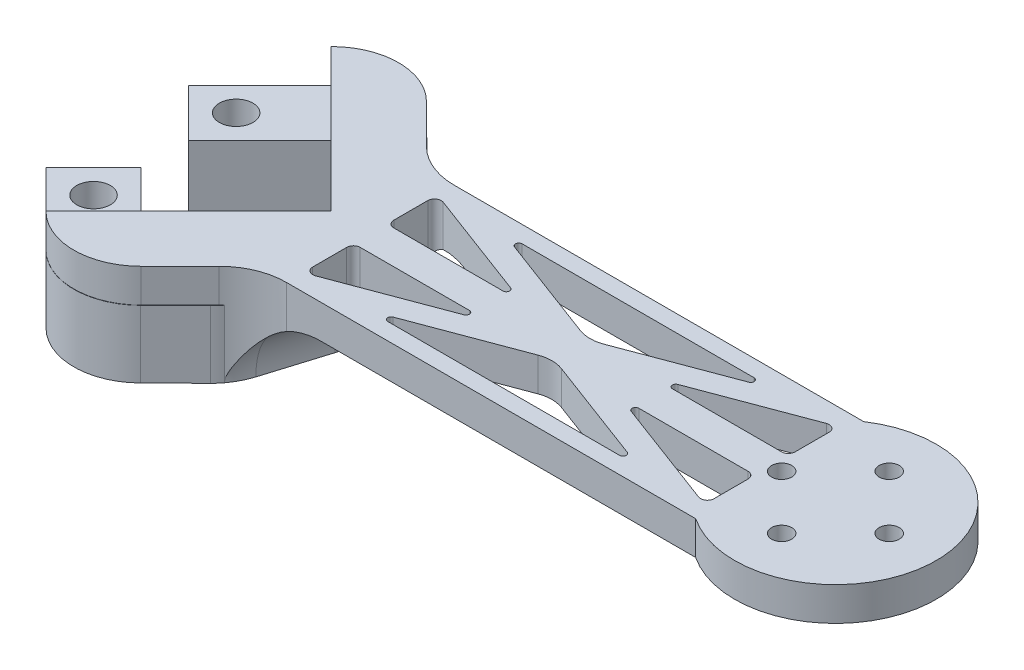
SolidWorks part; units mm, degrees
ref_plane "Front Plane" through (0, 0, 0) normal (0, 0, 1) x (1, 0, 0)
ref_plane "Top Plane" through (0, 0, 0) normal (0, 1, 0) x (1, 0, 0)
ref_plane "Right Plane" through (0, 0, 0) normal (1, 0, 0) x (0, 0, -1)
sketch "Sketch1" plane through (0, 0, 0) normal (0, 1, 0) x (1, 0, 0)
  line L0 (0, 0) -> (75, 0) construction
  line L1 (0, 0) -> (-21.2132, -21.2132) construction
  line L2 (0, 0) -> (-21.2132, 21.2132) construction
  line L3 (-21.2132, 21.2132) -> (-14.1314, 28.295) construction
  line L4 (-21.2132, -21.2132) -> (-14.1206, -28.3058) construction
  line L5 (0, -12.5) -> (0, 12.5) construction
  line L6 (0, 12.5) -> (66.7084, 12.5) construction
  line L7 (0, -12.5) -> (66.7084, -12.5) construction
  line L8 (-7.0496, -21.2347) -> (-1.2438, -15.4289)
  line L9 (-7.0603, 21.224) -> (-1.2653, 15.4289)
  line L10 (-21.2025, 21.224) -> (-21.2132, 21.2132)
  line L11 (-21.2132, 21.2132) -> (0, 0)
  line L12 (0, 0) -> (-21.2132, -21.2132)
  line L13 (-21.2132, -21.2132) -> (-21.1917, -21.2347)
  line L14 (5.8058, 12.5) -> (66.7084, 12.5)
  line L15 (5.8273, -12.5) -> (66.7084, -12.5)
  circle A0 centre (75, 0) radius 8 construction
  circle A1 centre (75, 0) radius 15 construction
  arc A2 (66.7084, 12.5) -> (66.7084, -12.5) centre (75, 0) cw
  arc A3 (-1.2653, 15.4289) -> (5.8058, 12.5) centre (5.8058, 22.5) ccw
  arc A4 (-1.2438, -15.4289) -> (5.8273, -12.5) centre (5.8273, -22.5) cw
  arc A5 (-21.1917, -21.2347) -> (-7.0496, -21.2347) centre (-14.1206, -14.1636) ccw
  arc A6 (-21.2025, 21.224) -> (-7.0603, 21.224) centre (-14.1314, 14.1529) cw
  circle A7 centre (67, 0) radius 1.5
  circle A8 centre (75, 8) radius 1.5
  circle A9 centre (83, 0) radius 1.5
  circle A10 centre (75, -8) radius 1.5
  point P5 (67, 0)
  point P6 (75, 8)
  point P7 (83, 0)
  point P8 (75, -8)
  point P19 (1.6636, 12.5)
  point P21 (0, 0)
  point P25 (1.6851, -12.5)
  dimension "D1" = 10
extrude "Boss-Extrude1" add sketch "Sketch1" along normal blind 5 contours A6 L10 L11 L12 L13 A5 L8 A4 L15 A2 L14 A3 L9 A10 A9 A8 A7
sketch "Sketch2" plane through (0, 5, 0) normal (0, 1, 0) x (1, 0, 0)
  line L0 (-1000, 0) -> (49000, 0) construction
  line L1 (5.8058, -987.5) -> (5.8058, 49012.5) construction
  line L2 (65.5, -1000) -> (65.5, 49000) construction
  line L3 (5.8058, 12.5) -> (66.7084, 12.5) construction
  line L4 (5.8058, 12.5) -> (5.8058, 10) construction
  line L5 (5.8058, 0) -> (5.8058, 2.5) construction
  line L6 (-994.1942, 10) -> (49005.8058, 10) construction
  line L7 (-994.1942, 2.5) -> (49005.8058, 2.5) construction
  line L8 (5.8058, 2.5) -> (65.5, 2.5) construction
  line L9 (5.8058, 2.5) -> (25.8058, 2.5) construction
  line L10 (65.5, 2.5) -> (45.5, 2.5) construction
  line L11 (35.6529, 10) -> (55.6529, 10) construction
  line L12 (35.6529, 10) -> (15.6529, 10) construction
  line L13 (5.8058, 8.557) -> (5.8058, 3.5)
  line L14 (6.8058, 2.5) -> (23.0484, 2.5)
  line L15 (23.224, 3.4682) -> (7.1569, 9.4933)
  line L16 (18.4102, 10) -> (52.8956, 10)
  line L17 (53.0711, 9.0318) -> (37.4085, 3.1584)
  line L18 (33.8973, 3.1584) -> (18.2347, 9.0318)
  line L19 (48.0818, 3.4682) -> (64.1489, 9.4933)
  line L20 (65.5, 8.557) -> (65.5, 3.5)
  line L21 (64.5, 2.5) -> (48.2573, 2.5)
  line L22 (65.5, -8.557) -> (65.5, -3.5)
  line L23 (48.0818, -3.4682) -> (64.1489, -9.4933)
  line L24 (64.5, -2.5) -> (48.2573, -2.5)
  line L25 (53.0711, -9.0318) -> (37.4085, -3.1584)
  line L26 (18.4102, -10) -> (52.8956, -10)
  line L27 (33.8973, -3.1584) -> (18.2347, -9.0318)
  line L28 (6.8058, -2.5) -> (23.0484, -2.5)
  line L29 (5.8058, -8.557) -> (5.8058, -3.5)
  line L30 (23.224, -3.4682) -> (7.1569, -9.4933)
  arc A0 (7.1569, 9.4933) -> (5.8058, 8.557) centre (6.8058, 8.557) ccw
  arc A1 (64.5, 2.5) -> (65.5, 3.5) centre (64.5, 3.5) ccw
  arc A2 (65.5, 8.557) -> (64.1489, 9.4933) centre (64.5, 8.557) ccw
  arc A3 (5.8058, 3.5) -> (6.8058, 2.5) centre (6.8058, 3.5) ccw
  arc A4 (37.4085, 3.1584) -> (33.8973, 3.1584) centre (35.6529, 7.84) cw
  arc A5 (48.2573, 2.5) -> (48.0818, 3.4682) centre (48.2573, 3) cw
  arc A6 (53.0711, 9.0318) -> (52.8956, 10) centre (52.8956, 9.5) ccw
  arc A7 (18.2347, 9.0318) -> (18.4102, 10) centre (18.4102, 9.5) cw
  arc A8 (23.224, 3.4682) -> (23.0484, 2.5) centre (23.0484, 3) cw
  arc A9 (65.5, -8.557) -> (64.1489, -9.4933) centre (64.5, -8.557) cw
  arc A10 (64.5, -2.5) -> (65.5, -3.5) centre (64.5, -3.5) cw
  arc A11 (48.2573, -2.5) -> (48.0818, -3.4682) centre (48.2573, -3) ccw
  arc A12 (53.0711, -9.0318) -> (52.8956, -10) centre (52.8956, -9.5) cw
  arc A13 (37.4085, -3.1584) -> (33.8973, -3.1584) centre (35.6529, -7.84) ccw
  arc A14 (18.2347, -9.0318) -> (18.4102, -10) centre (18.4102, -9.5) ccw
  arc A15 (5.8058, -3.5) -> (6.8058, -2.5) centre (6.8058, -3.5) cw
  arc A16 (7.1569, -9.4933) -> (5.8058, -8.557) centre (6.8058, -8.557) cw
  arc A17 (23.224, -3.4682) -> (23.0484, -2.5) centre (23.0484, -3) ccw
  point P14 (65.5, 10)
  point P19 (65.5, 2.5)
  point P20 (35.6529, 2.5)
  point P37 (65.5, 10)
  point P43 (35.6529, 2.5)
  dimension "D3" = 1
  dimension "D4" = 5
  dimension "D5" = 0.5
  dimension "D1" = 59.6942
  dimension "D2" = 12.5
extrude "Cut-Extrude2" cut sketch "Sketch2" against normal blind 5
sketch "Sketch3" plane through (0, 0, 0) normal (0, -1, 0) x (1, 0, 0)
  line L0 (0, 0) -> (-14.1421, -14.1421) construction
  line L1 (-21.2132, -21.2132) -> (0, 0) construction
  line L2 (0, 0) -> (-14.1421, 14.1421) construction
  line L3 (0, 0) -> (-21.2132, 21.2132) construction
  line L4 (-14.1421, -14.1421) -> (0, 0)
  line L5 (-14.1421, -14.1421) -> (-21.2132, -7.0711)
  line L6 (0, 0) -> (-14.1421, 14.1421)
  line L7 (-21.2132, 7.0711) -> (-14.1421, 14.1421)
  line L8 (-21.1917, 21.2347) -> (-21.1552, 21.2712)
  line L9 (-7.0715, 21.3293) -> (-1.8046, 16.1484)
  line L10 (0.7427, 11.9534) -> (3.5104, 2.9356)
  line L11 (3.5095, -2.9354) -> (0.7421, -11.9426)
  line L12 (-21.1917, 21.2347) -> (-31.8198, 10.6066)
  line L13 (-31.8198, -10.6066) -> (-21.159, -21.2674)
  line L14 (-7.0715, -21.3215) -> (-1.8004, -16.1309)
  line L15 (-31.8198, 10.6066) -> (-31.8198, -10.6066)
  line L16 (-728.32, -700.0357) -> (34627.0191, 34655.3033) construction
  line L17 (-728.32, 700.0357) -> (34627.0191, -34655.3033) construction
  line L18 (-21.2132, 7.0711) -> (-28.2843, 0)
  line L19 (-28.2843, 0) -> (-21.2132, -7.0711)
  arc A1 (-1.2438, 15.4289) -> (5.8273, 12.5) centre (5.8273, 22.5) ccw construction
  arc A2 (5.8058, -12.5) -> (-1.2653, -15.4289) centre (5.8058, -22.5) ccw construction
  arc A3 (3.5104, 2.9356) -> (3.5095, -2.9354) centre (-6.0495, 0.0016) cw
  arc A4 (-1.8046, 16.1484) -> (0.7427, 11.9534) centre (-8.8172, 9.0193) cw
  arc A5 (0.7421, -11.9426) -> (-1.8004, -16.1309) centre (-8.8169, -9.0057) cw
  arc A6 (-21.159, -21.2674) -> (-7.0715, -21.3215) centre (-14.088, -14.1963) ccw
  arc A7 (-21.1552, 21.2712) -> (-7.0715, 21.3293) centre (-14.0841, 14.2002) cw
  point P10 (-28.2843, 0)
  point P24 (-42.4264, 0)
  point P31 (0, 14.3733)
  point P34 (0, -14.3579)
  dimension "D2" = 10
extrude "Boss-Extrude2" add sketch "Sketch3" along normal blind 35 contours L14 A5 L11 A3 L10 A4 L9 A7 L8 L12 L15 L13 A6 | L4 L6 L7 L18 L19 L5
sketch "Sketch4" plane through (0, -35, 0) normal (0, -1, 0) x (1, 0, 0)
  line L0 (0, 0) -> (-17.6777, -17.6777) construction
  line L1 (0, 0) -> (-17.6777, 17.6777) construction
  line L2 (-17.6777, -17.6777) -> (-24.7487, -10.6066) construction
  line L3 (-17.6777, 17.6777) -> (-24.7487, 10.6066) construction
  circle A0 centre (-24.7487, 10.6066) radius 2.5
  circle A1 centre (-24.7487, -10.6066) radius 2.5
extrude "Cut-Extrude3" cut sketch "Sketch4" against normal through all both and the other way through all
sketch "Sketch5" plane through (0, -35, 0) normal (0, -1, 0) x (1, 0, 0)
  line L0 (0, 0) -> (-21.1552, 21.2712)
  line L1 (0, 0) -> (-21.159, -21.2674)
  line L2 (-7.0169, -21.159) -> (-3.7307, -17.8729)
  line L3 (-7.013, 21.1552) -> (-3.7307, 17.8728)
  line L4 (3.5917, 0.1905) -> (3.5916, -0.1998)
  arc A0 (-21.1552, 21.2712) -> (-7.013, 21.1552) centre (-14.1421, 14.1421) cw
  arc A1 (-21.159, -21.2674) -> (-7.0169, -21.159) centre (-14.1421, -14.1421) ccw
  arc A2 (-3.7307, -17.8729) -> (3.5916, -0.1998) centre (-21.4084, -0.1952) ccw
  arc A3 (-3.7307, 17.8728) -> (3.5917, 0.1905) centre (-21.4083, 0.1951) cw
  dimension "D1" = 25
extrude "Boss-Extrude3" add sketch "Sketch5" along normal blind 5
fillet "Fillet1" radius 10 13 edges at (6.0987, 0, 2.7929) (6.2362, 0, 9.3789) (5.8058, 0, 6.0285) (6.2362, 0, -9.3789) (6.0987, 0, -2.7929) (5.8058, 0, -6.0285) (2.2627, 0, -13.1487) (2.2626, 0, 13.1569) (0.0893, 0, 13.5663) (2.1265, 0, 7.4445) (3.9505, 0, 0.0001) (2.1258, 0, -7.439) (0.0938, 0, -13.5444)
sketch "Sketch6" plane through (0, -35, 0) normal (0, -1, 0) x (1, 0, 0)
  line L0 (-31.8198, -10.6066) -> (-24.7487, -3.5355)
  line L1 (-14.1421, -14.1421) -> (-28.2843, 0) construction
  line L2 (-31.8198, 10.6066) -> (-24.7487, 3.5355)
  line L3 (-14.1421, 14.1421) -> (-28.2843, 0) construction
  line L4 (-31.8198, 10.6066) -> (-31.8198, -10.6066)
  line L5 (-24.7487, -3.5355) -> (-28.2843, 0)
  line L6 (-28.2843, 0) -> (-24.7487, 3.5355)
extrude "Cut-Extrude4" cut sketch "Sketch6" against normal through all both and the other way through all
sketch "Sketch8" plane through (-21.2132, 0, 21.2132) normal (-0.7071, 0, 0.7071) x (0.7071, 0, 0.7071)
  line L0 (-15, 0) -> (-15, -10) construction
  line L1 (-15, -35) -> (-15, 0) construction
  line L2 (-1015, -10) -> (48985, -10) construction
  line L4 (-39.3962, -10) -> (20.2307, -10)
  line L5 (-39.3962, -10) -> (-39.3962, -42.7942)
  line L6 (-39.3962, -42.7942) -> (20.2307, -42.7942)
  line L7 (20.2307, -10) -> (20.2307, -42.7942)
  line L8 (-39.3962, -10) -> (20.2307, -42.7942) construction
  line L9 (-39.3962, -42.7942) -> (20.2307, -10) construction
  point P11 (-9.5827, -26.3971)
extrude "Cut-Extrude6" cut sketch "Sketch8" against normal through all both and the other way through all
